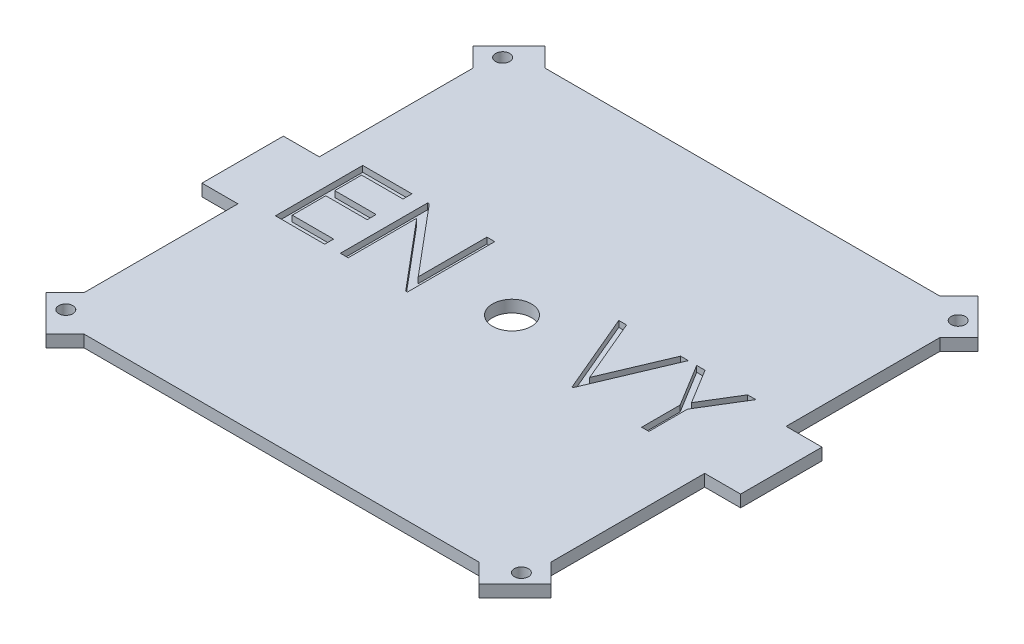
SolidWorks part; units mm, degrees
ref_plane "Front Plane" through (0, 0, 0) normal (0, 0, 1) x (1, 0, 0)
ref_plane "Top Plane" through (0, 0, 0) normal (0, 1, 0) x (1, 0, 0)
ref_plane "Right Plane" through (0, 0, 0) normal (1, 0, 0) x (0, 0, -1)
sketch "Sketch1" plane through (0, 0, 0) normal (0, 1, 0) x (1, 0, 0)
  line L0 (235.6983, 13.3827) -> (243.3183, 5.7627) construction
  line L1 (243.3183, 5.7627) -> (243.3183, -26.8763) construction
  line L2 (243.3183, -76.7873) -> (243.3183, -44.1483) construction
  line L3 (243.3183, -76.7873) -> (235.6983, -84.4073) construction
  line L4 (151.8783, -84.4073) -> (235.6983, -84.4073) construction
  line L5 (151.8783, -84.4073) -> (144.2583, -76.7873) construction
  line L6 (144.2583, -76.7873) -> (144.2583, -44.1483) construction
  line L7 (144.2583, 5.7627) -> (144.2583, -26.8763) construction
  line L8 (144.2583, 5.7627) -> (151.8783, 13.3827) construction
  line L9 (151.8783, 13.3827) -> (235.6983, 13.3827) construction
  line L10 (235.6983, 13.3827) -> (243.3183, 5.7627)
  line L11 (243.3183, 5.7627) -> (243.3183, -26.8763)
  line L12 (243.3183, -76.7873) -> (243.3183, -44.1483)
  line L13 (243.3183, -76.7873) -> (235.6983, -84.4073)
  line L14 (151.8783, -84.4073) -> (235.6983, -84.4073)
  line L15 (151.8783, -84.4073) -> (144.2583, -76.7873)
  line L16 (144.2583, -76.7873) -> (144.2583, -44.1483)
  line L17 (144.2583, 5.7627) -> (144.2583, -26.8763)
  line L18 (144.2583, 5.7627) -> (151.8783, 13.3827)
  line L19 (151.8783, 13.3827) -> (235.6983, 13.3827)
  line L20 (144.2583, -26.8763) -> (144.2583, -44.1483)
  line L21 (243.3183, -26.8763) -> (243.3183, -44.1483)
  line L22 (140.2172, 9.8038) -> (147.8372, 17.4238)
  line L23 (239.7394, 17.4238) -> (247.3594, 9.8038)
  line L24 (247.3594, -80.8284) -> (239.7394, -88.4484)
  line L25 (147.8372, -88.4484) -> (140.2172, -80.8284)
  line L26 (140.2172, 9.8038) -> (144.2583, 5.7627)
  line L27 (147.8372, 17.4238) -> (151.8783, 13.3827)
  line L28 (235.6983, 13.3827) -> (243.3183, 5.7627)
  line L29 (235.6983, 13.3827) -> (239.7394, 17.4238)
  line L30 (243.3183, 5.7627) -> (247.3594, 9.8038)
  line L31 (239.7394, 17.4238) -> (247.3594, 9.8038)
  line L32 (144.2583, -76.7873) -> (151.8783, -84.4073)
  line L33 (144.2583, -76.7873) -> (140.2172, -80.8284)
  line L34 (151.8783, -84.4073) -> (147.8372, -88.4484)
  line L35 (140.2172, -80.8284) -> (147.8372, -88.4484)
  line L36 (243.3183, -76.7873) -> (235.6983, -84.4073)
  line L37 (243.3183, -76.7873) -> (247.3594, -80.8284)
  line L38 (235.6983, -84.4073) -> (239.7394, -88.4484)
  line L39 (247.3594, -80.8284) -> (239.7394, -88.4484)
  line L44 (144.2583, -31.7023) -> (144.2583, -39.3223)
  line L45 (144.2583, -31.7023) -> (174.7383, -31.7023)
  line L46 (144.2583, -39.3223) -> (174.7383, -39.3223)
  line L47 (174.7383, -31.7023) -> (174.7383, -39.3223)
  line L48 (193.7883, 13.3827) -> (193.7883, 23.3481)
  line L49 (243.3183, -39.3223) -> (212.8383, -39.3223)
  line L50 (212.8383, -31.7023) -> (212.8383, -39.3223)
  line L51 (243.3183, -31.7023) -> (212.8383, -31.7023)
  line L52 (136.6383, -35.5123) -> (68.6957, -35.5123)
  line L54 (144.2583, -43.1323) -> (144.2583, -27.8923)
  line L58 (137.6543, -43.1323) -> (153.9103, -43.1323) construction
  line L59 (137.6543, -27.8923) -> (153.9103, -27.8923) construction
  line L61 (243.3183, -44.1483) -> (250.9383, -44.1483)
  line L62 (250.9383, -26.8763) -> (250.9383, -44.1483)
  line L63 (243.3183, -26.8763) -> (250.9383, -26.8763)
  line L64 (144.2583, -26.8763) -> (144.2583, -44.1483)
  line L65 (144.2583, -26.8763) -> (136.6383, -26.8763)
  line L68 (144.2583, -44.1483) -> (136.6383, -44.1483)
  line L69 (136.6383, -26.8763) -> (136.6383, -44.1483)
  line L70 (136.6383, -26.8763) -> (136.6383, -32.4643) construction
  circle A0 centre (193.7883, -35.5123) radius 4.1275
  point P20 (174.7383, -35.5123)
  point P23 (144.2583, -35.5123)
  dimension "D4" = 8.255
  dimension "D1" = 5.715
  dimension "D2" = 30.48
  dimension "D3" = 7.62
extrude "Boss-Extrude1" add sketch "Sketch1" along normal blind 2.54 contours L27 L22 L26 L18 | L21 L11 L10 L19 L18 L17 L20 L16 L15 L14 L13 L12 | L34 L15 L33 L25 | L13 L38 L24 L37 | L10 L30 L23 L29 | L20 | L21 | L20 | L21 region at (241.5288, 0, -11.5933) region at (238.524, 0, -8.5884) region at (247.1283, 0, 35.5123) region at (146.0477, 0, -11.5933) region at (228.0783, 0, 35.5123) region at (140.4483, 0, 35.5123) region at (241.5288, 0, 82.6179) region at (159.4983, 0, 35.5123) region at (146.0477, 0, 82.6179)
sketch "Sketch2" plane through (0, 2.54, 0) normal (0, 1, 0) x (1, 0, 0)
  line L0 (140.2172, 9.8038) -> (147.8372, 17.4238) construction
  line L1 (193.7883, 18.4627) -> (193.7883, 24.9503)
  line L2 (92.1883, -35.5123) -> (28.5523, -35.5123)
  line L4 (147.8372, 17.4238) -> (151.8783, 13.3827) construction
  circle A0 centre (145.4484, 10.8323) radius 1.5
  circle A1 centre (242.1282, 10.8323) radius 1.5
  circle A2 centre (242.1282, -81.8569) radius 1.5
  circle A3 centre (145.4484, -81.8569) radius 1.5
  dimension "D1" = 3
  dimension "D2" = 2.9718
  dimension "D3" = 6.35
extrude "Cut-Extrude1" cut sketch "Sketch2" against normal through all contours A0 | A1 | A2 | A3 region at (145.4484, 2.54, -10.8323) region at (242.1282, 2.54, -10.8323) region at (242.1282, 2.54, 81.8569) region at (145.4484, 2.54, 81.8569)
sketch "Sketch3" plane through (0, 2.54, 0) normal (0, 1, 0) x (1, 0, 0)
  line L2 (250.9383, -26.8763) -> (250.9383, -44.1483) construction
  circle A0 centre (193.7883, -35.5123) radius 4.1275 construction
  text T0 "EN" font "Century Gothic" height in points 70
  text T1 "VY" font "Century Gothic" height in points 65
  dimension "D1" = 45.72
  dimension "D2" = 45.72
extrude "Cut-Extrude2" cut sketch "Sketch3" against normal blind 1.27
extrude "Boss-Extrude2" add sketch "Sketch1<5>" against normal blind 3.556 contours L47 L45 L20 L46 | L21 L51 L50 L49 region at (228.0783, 0, 35.5123) region at (159.4983, 0, 35.5123)
sketch "Sketch1<5>" plane through (0, 0, 0) normal (0, 1, 0) x (1, 0, 0) same geometry as "Sketch1"
fillet "Fillet1" radius 2.54 4 edges at (228.0783, -3.556, 39.3223) (228.0783, -3.556, 31.7023) (159.4983, -3.556, 31.7023) (159.4983, -3.556, 39.3223)
